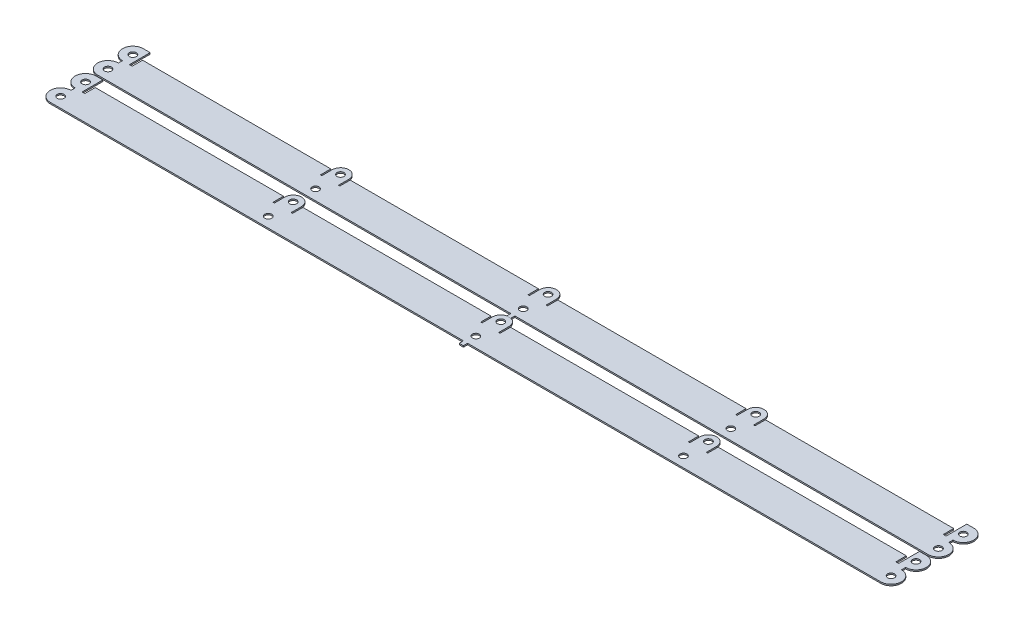
SolidWorks part; units mm, degrees
ref_plane "Front Plane" through (0, 0, 0) normal (0, 0, 1) x (1, 0, 0)
ref_plane "Top Plane" through (0, 0, 0) normal (0, 1, 0) x (1, 0, 0)
ref_plane "Right Plane" through (0, 0, 0) normal (1, 0, 0) x (0, 0, -1)
sketch "Sketch1" plane through (0, 0, 0) normal (0, 1, 0) x (1, 0, 0)
  line L0 (-300, 0) -> (300, 0) construction
  line L1 (-300, 7.5) -> (300, 7.5) construction
  line L2 (-300, 7.5) -> (-300, -7.5) construction
  line L3 (-300, -7.5) -> (300, -7.5)
  line L4 (300, 7.5) -> (300, -7.5) construction
  line L5 (-300, 7.5) -> (300, -7.5) construction
  line L6 (-300, -7.5) -> (300, 7.5) construction
  line L9 (-300, 25.5) -> (300, 25.5) construction
  line L12 (-300, 7.5) -> (-300, 10.5)
  line L15 (300, 7.5) -> (300, 10.5)
  line L19 (0, 0) -> (0, 25.5) construction
  line L21 (300, 10.5) -> (300, 25.5) construction
  line L24 (-300, 10.5) -> (-300, 25.5) construction
  line L25 (-300, 18) -> (300, 18) construction
  line L52 (295, 25.5) -> (300, 25.5)
  line L53 (-300, 10.5) -> (300, 10.5) construction
  line L54 (-295, 10.5) -> (-295, 25.5)
  line L55 (-295, 25.5) -> (-300, 25.5)
  line L56 (-295, 10.5) -> (-293, 10.5)
  line L60 (-157, 10.5) -> (-156, 10.5)
  line L61 (-156, 10.5) -> (-156, 18)
  line L62 (-144, 18) -> (-144, 10.5)
  line L63 (-144, 10.5) -> (-143, 10.5)
  line L66 (-7, 10.5) -> (-6, 10.5)
  line L67 (-6, 10.5) -> (-6, 18)
  line L68 (6, 18) -> (6, 10.5)
  line L69 (6, 10.5) -> (7, 10.5)
  line L72 (143, 10.5) -> (144, 10.5)
  line L73 (144, 10.5) -> (144, 18)
  line L74 (156, 18) -> (156, 10.5)
  line L75 (156, 10.5) -> (157, 10.5)
  line L78 (293, 10.5) -> (295, 10.5)
  line L79 (295, 10.5) -> (295, 25.5)
  line L80 (-293, 18) -> (-157, 18)
  line L81 (293, 10.5) -> (293, 18)
  line L82 (-143, 18) -> (-7, 18)
  line L83 (293, 18) -> (157, 18)
  line L84 (157, 18) -> (157, 10.5)
  line L85 (143, 10.5) -> (143, 18)
  line L86 (143, 18) -> (7, 18)
  line L87 (7, 18) -> (7, 10.5)
  line L88 (-7, 10.5) -> (-7, 18)
  line L89 (-293, 10.5) -> (-293, 18)
  line L90 (-157, 10.5) -> (-157, 18)
  line L91 (-143, 10.5) -> (-143, 18)
  line L92 (-1.5, -7.5) -> (-1.5, -10.5)
  line L93 (-1.5, -10.5) -> (1.5, -10.5)
  line L94 (1.5, -10.5) -> (1.5, -7.5)
  line L95 (0, 0) -> (0, -10.5) construction
  circle A0 centre (0, 0) radius 2.5
  arc A2 (-300, 7.5) -> (-300, -7.5) centre (-300, 0) ccw
  arc A3 (300, 7.5) -> (300, -7.5) centre (300, 0) cw
  circle A4 centre (150, 0) radius 2.5
  circle A5 centre (-150, 0) radius 2.5
  circle A6 centre (-300, 0) radius 2.5
  circle A7 centre (300, 0) radius 2.5
  arc A8 (300, 10.5) -> (300, 25.5) centre (300, 18) ccw
  arc A9 (-300, 25.5) -> (-300, 10.5) centre (-300, 18) ccw
  circle A10 centre (0, 18) radius 2.5
  circle A11 centre (-150, 18) radius 2.5
  circle A12 centre (-300, 18) radius 2.5
  circle A13 centre (0, 18) radius 2.5
  circle A14 centre (150, 18) radius 2.5
  circle A15 centre (300, 18) radius 2.5
  arc A16 (144, 18) -> (156, 18) centre (150, 18) cw
  arc A17 (-6, 18) -> (6, 18) centre (0, 18) cw
  arc A18 (-144, 18) -> (-156, 18) centre (-150, 18) ccw
  dimension "D1" = 5
  dimension "D2" = 600
  dimension "D3" = 3
  dimension "D4" = 15
  dimension "D5" = 18
  dimension "D6" = 2
  dimension "D7" = 3
  dimension "D9" = 5
  dimension "D10" = 12
  dimension "D13" = 1
  dimension "D14" = 3
  dimension "D15" = 3
  dimension "D8" = 3
  dimension "D11" = 2
  dimension "D12" = 2
extrude "Boss-Extrude1" add sketch "Sketch1" along normal blind 1 contours L62 A18 L61 L60 L90 L80 L89 L56 L54 L55 A9 L12 A2 L3 A3 L15 A8 L52 L79 L78 L81 L83 L84 L75 L74 A16 L73 L72 L85 L86 L87 L69 L68 A17 L67 L66 L88 L82 L91 L63 A0 A4 A5 A6 | L93 L94 L3 L92 region at (0, 0, -5.4898) region at (0, 0, 9)
pattern_linear "LPattern1" count 2 spacing 34.2 along (0, 0, -1) of "Boss-Extrude1"
